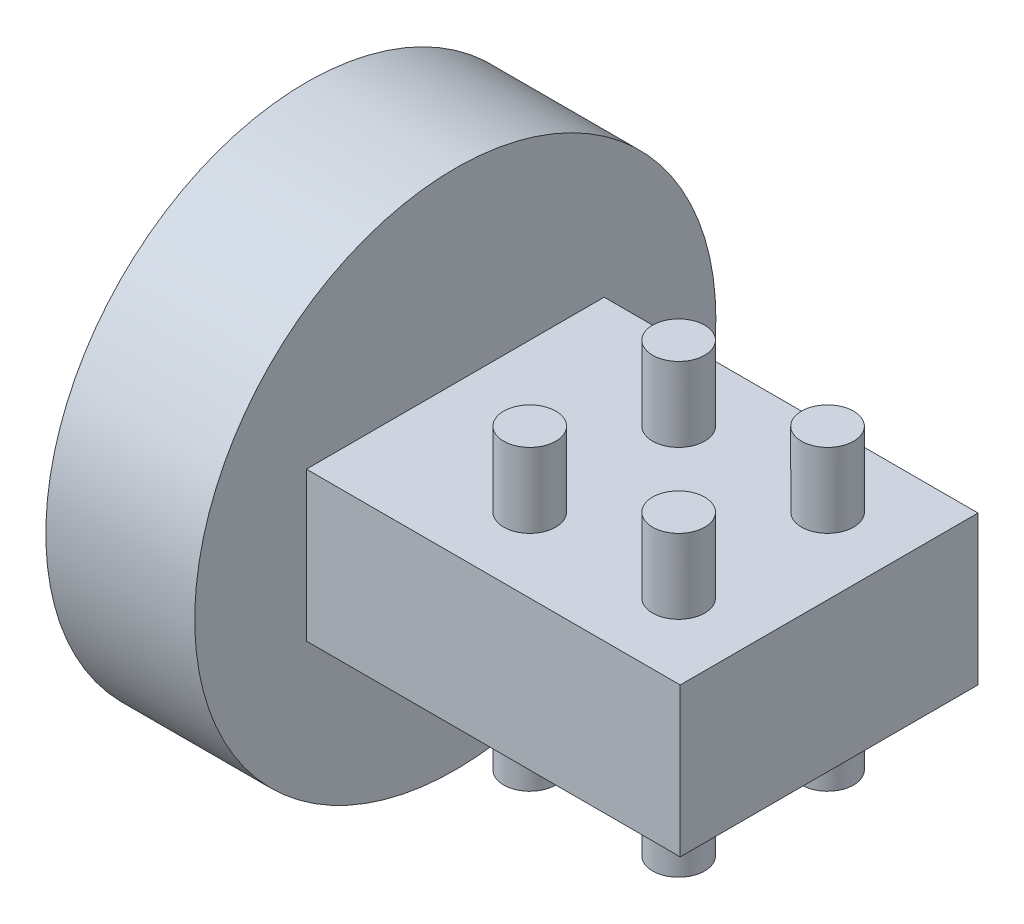
SolidWorks part; units mm, degrees
ref_plane "Front Plane" through (0, 0, 0) normal (0, 0, 1) x (1, 0, 0)
ref_plane "Top Plane" through (0, 0, 0) normal (0, 1, 0) x (1, 0, 0)
ref_plane "Right Plane" through (0, 0, 0) normal (1, 0, 0) x (0, 0, -1)
sketch "Sketch1" plane through (0, 0, 0) normal (1, 0, 0) x (0, 0, -1)
  circle A0 centre (0, 0) radius 35
  dimension "D1" = 70
extrude "Boss-Extrude1" add sketch "Sketch1" along normal blind 20 contours A0
sketch "Sketch2" plane through (0, 0, 0) normal (1, 0, 0) x (0, 0, -1)
  circle A0 centre (0, 0) radius 25
  dimension "D1" = 50
extrude "Cut-Extrude1" cut sketch "Sketch2" along normal blind 10
sketch "Sketch3" plane through (0, 0, 0) normal (0, 1, 0) x (1, 0, 0)
  line L1 (0.2085, -20) -> (70.2085, -20)
  line L2 (0.2085, -20) -> (0.2085, 20)
  line L3 (0.2085, 20) -> (70.2085, 20)
  line L4 (70.2085, -20) -> (70.2085, 20)
  line L5 (0.2085, -20) -> (70.2085, 20) construction
  line L6 (0.2085, 20) -> (70.2085, -20) construction
  point P0 (35.2085, 0)
  dimension "D1" = 70
  dimension "D2" = 40
  dimension "D3" = 0
extrude "Boss-Extrude2" add sketch "Sketch3" along normal blind 10 and the other way blind 10
sketch "Sketch5" plane through (0, 0, 0) normal (0, 1, 0) x (1, 0, 0)
  circle A0 centre (40, -10) radius 3.5
  circle A1 centre (40, 10) radius 3.5
  circle A2 centre (60, 10) radius 3.5
  circle A3 centre (60, -10) radius 3.5
  dimension "D2" = 7
  dimension "D5" = 7
  dimension "D9" = 7
  dimension "D10" = 7
  dimension "D1" = 10
  dimension "D3" = 60
  dimension "D4" = 10
  dimension "D6" = 40
  dimension "D7" = 10
  dimension "D8" = 10
  dimension "D11" = 60
  dimension "D12" = 40
extrude "Boss-Extrude3" add sketch "Sketch5" along normal blind 20 and the other way blind 20
sketch "Sketch6" plane through (10, 0, 0) normal (-1, 0, 0) x (0, 0, 1)
  circle A0 centre (0, 0) radius 25
extrude "Cut-Extrude2" cut sketch "Sketch6" along normal blind 27
